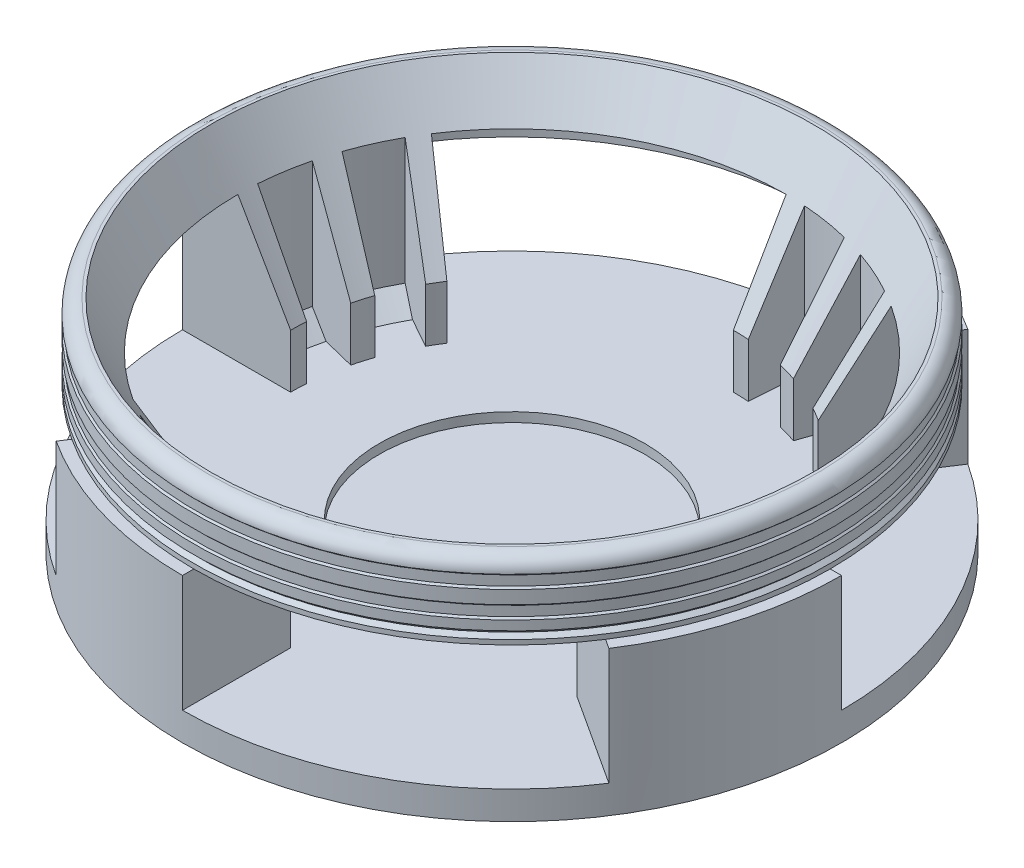
SolidWorks part; units mm, degrees
ref_plane "前视基准面" through (0, 0, 0) normal (0, 0, 1) x (1, 0, 0)
ref_plane "上视基准面" through (0, 0, 0) normal (0, 1, 0) x (1, 0, 0)
ref_plane "右视基准面" through (0, 0, 0) normal (1, 0, 0) x (0, 0, -1)
sketch "草图1" plane through (0, 0, 0) normal (0, 1, 0) x (1, 0, 0)
  circle A0 centre (0, 0) radius 35
  dimension "D1" = 70
extrude "凸台-拉伸1" add sketch "草图1" along normal blind 3
sketch "草图2" plane through (0, 3, 0) normal (0, 1, 0) x (1, 0, 0)
  line L0 (0, 32) -> (0, 35)
  line L1 (17.4284, 26.8375) -> (19.0624, 29.3535)
  line L2 (32, 0) -> (35, 0)
  line L3 (26.8375, -17.4284) -> (29.3535, -19.0624)
  line L4 (0, -32) -> (0, -35)
  line L5 (-17.4284, -26.8375) -> (-19.0624, -29.3535)
  line L6 (-32, 0) -> (-35, 0)
  line L7 (-26.8375, 17.4284) -> (-29.3535, 19.0624)
  circle A0 centre (0, 0) radius 35
  circle A1 centre (0, 0) radius 32
  circle A2 centre (0, 0) radius 35 construction
  point P21 (0, 0)
  point P25 (0, 0)
  dimension "D1" = 3
  dimension "D3" = 33
  dimension "D2" = 33
  dimension "D4" = 33
  dimension "D5" = 33
extrude "凸台-拉伸2" add sketch "草图2" along normal blind 20.4
sketch "草图3" plane through (0, 3, 0) normal (0, 1, 0) x (1, 0, 0)
  circle A0 centre (0, 0) radius 14.1
  dimension "D1" = 28.2
extrude "切除-拉伸1" cut sketch "草图3" against normal blind 1
sketch "草图4" plane through (0, 23.4, 0) normal (0, 1, 0) x (1, 0, 0)
  circle A0 centre (0, 0) radius 35
  circle A1 centre (0, 0) radius 33.8
  arc A3 (29.3535, -19.0624) -> (35, 0) centre (0, 0) ccw construction
  dimension "D1" = 1.2
extrude "切除-拉伸2" cut sketch "草图4" against normal blind 8
fillet "圆角1" radius 1.5 4 edges at (-32.4081, 23.4, -9.5997) (9.5997, 23.4, -32.4081) (32.4081, 23.4, 9.5997) (-9.5997, 23.4, 32.4081)
chamfer "倒角1" distance 20.4 angle 30 4 edges at (9.0885, 3, -30.6822) (-9.0885, 3, 30.6822) (30.6822, 3, 9.0885) (-30.6822, 3, -9.0885) first distance on face at (8.9014, 13.2, -30.0505) first distance on face at (-8.9014, 13.2, 30.0505) first distance on face at (30.0505, 13.2, 8.9014) first distance on face at (-30.0505, 13.2, -8.9014)
sketch "草图10" plane through (0, 0, 0) normal (0.8387, 0, 0.5446) x (0.5446, 0, -0.8387)
  line L0 (32, 23.4) -> (29.1132, 18.4)
  line L1 (33.8, 21.9) -> (33.8, 15.4)
  line L2 (32, 23.4) -> (32.3, 23.4)
  line L3 (29.1132, 18.4) -> (30.2679, 18.4)
  line L4 (30.2679, 18.4) -> (31.3732, 20.3144)
  line L5 (33.8, 15.4) -> (32.3, 15.4)
  line L6 (32.3, 15.4) -> (32.3, 20.0661)
  line L7 (33.8, 21.9) -> (33.8, 15.4) construction
  line L8 (32, 23.4) -> (26.8375, 23.4) construction
  line L9 (32, 23.4) -> (20.2221, 3) construction
  line L10 (33.8, 15.4) -> (35, 15.4) construction
  line L12 (0, 0) -> (0, 39.3433) construction
  arc A0 (32.3, 20.0661) -> (31.3732, 20.3144) centre (31.8033, 20.0661) ccw
  arc A1 (33.8, 21.9) -> (32.3, 23.4) centre (32.3, 21.9) ccw
  arc A2 (33.8, 21.9) -> (32.3, 23.4) centre (32.3, 21.9) ccw construction
  dimension "D1" = 5
  dimension "D2" = 1
  dimension "D3" = 1.9
revolve "旋转2" add sketch "草图10" angle 360 about L12
sketch "草图6" plane through (0, 23.4, 0) normal (0, 1, 0) x (1, 0, 0)
  line L0 (0, 20.2221) -> (0, 29.1132)
  line L1 (1.4106, 20.1728) -> (2.0308, 29.0423)
  line L2 (9.8038, 17.6866) -> (14.1144, 25.463)
  line L3 (11.0137, 16.9596) -> (15.8562, 24.4164)
  line L4 (7.0431, 28.2485) -> (4.8922, 19.6214)
  line L5 (6.5837, 19.1203) -> (9.4783, 27.5271)
  line L6 (16.9596, -11.0137) -> (24.4164, -15.8562)
  line L7 (17.6866, -9.8038) -> (25.463, -14.1144)
  line L8 (19.1203, -6.5837) -> (27.5271, -9.4783)
  line L9 (28.2485, -7.0431) -> (19.6214, -4.8922)
  line L10 (20.1728, -1.4106) -> (29.0423, -2.0308)
  line L11 (20.2221, 0) -> (29.1132, 0)
  line L12 (-11.0137, -16.9596) -> (-15.8562, -24.4164)
  line L13 (-9.8038, -17.6866) -> (-14.1144, -25.463)
  line L14 (-6.5837, -19.1203) -> (-9.4783, -27.5271)
  line L15 (-7.0431, -28.2485) -> (-4.8922, -19.6214)
  line L16 (-21.6701, -19.4419) -> (-21.6916, -19.4749)
  line L17 (-1.4106, -20.1728) -> (-2.0308, -29.0423)
  line L18 (0, -20.2221) -> (0, -29.1132)
  line L19 (-16.9596, 11.0137) -> (-24.4164, 15.8562)
  line L20 (-17.6866, 9.8038) -> (-25.463, 14.1144)
  line L21 (-19.1203, 6.5837) -> (-27.5271, 9.4783)
  line L22 (-28.2485, 7.0431) -> (-19.6214, 4.8922)
  line L23 (-20.1728, 1.4106) -> (-29.0423, 2.0308)
  line L24 (-20.2221, 0) -> (-29.1132, 0)
  circle A0 centre (0, 0) radius 29.1132
  circle A1 centre (0, 0) radius 20.2221
  arc A2 (29.1132, 0) -> (15.8562, 24.4164) centre (0, 0) ccw construction
  arc A5 (11.0137, 16.9596) -> (0, 20.2221) centre (0, 0) ccw construction
  point P60 (0, 0)
  point P61 (0, 0)
  point P65 (0, 0)
  point P74 (-3.092, 2.2023)
  point P123 (0, 0)
  dimension "D1" = 4
  dimension "D2" = 4
  dimension "D3" = 10
  dimension "D4" = 10
  dimension "D5" = 4
extrude "切除-拉伸3" cut sketch "草图6" against normal up to surface (20.4 mm away) contours A1 L22 A0 L23 | A1 L20 A0 L21 | A1 L13 A0 L14 | A1 L15 A0 L17 | A1 L7 A0 L8 | A1 L9 A0 L10 | A1 L2 A0 L5 | A1 L4 A0 L1 up to face at (0, 3, 14.1)
sketch "草图7" plane through (0, 23.4, 0) normal (0, 1, 0) x (1, 0, 0)
  circle A3 centre (0, 0) radius 23.5132
  arc A4 (29.1132, 0) -> (15.8562, 24.4164) centre (0, 0) ccw construction
  dimension "D1" = 5.6
extrude "切除-拉伸4" cut sketch "草图7" against normal up to surface (20.4 mm away) up to face at (0, 3, 14.1)
chamfer "倒角2" distance 2 angle 45 8 edges at (26.5963, 3, 11.8414) (-4.5543, 3, 28.7548) (-11.8414, 3, 26.5963) (-26.5963, 3, -11.8414) (4.5543, 3, -28.7548) (11.8414, 3, -26.5963) (28.7548, 3, 4.5543) (-28.7548, 3, -4.5543)
sketch "草图11" plane through (0, 0, 0) normal (0.5446, 0, -0.8387) x (-0.8387, 0, -0.5446)
  line L0 (33.8, 21.9) -> (33.62, 21.72)
  line L1 (33.8, 15.4) -> (33.8, 21.9) construction
  line L2 (33.62, 21.72) -> (33.62, 20.68)
  line L3 (33.62, 20.68) -> (33.8, 20.5)
  line L4 (33.8, 20.5) -> (33.8, 21.9)
  line L5 (33.8, 19.1) -> (33.62, 18.92)
  line L6 (33.62, 18.92) -> (33.62, 17.88)
  line L7 (33.62, 17.88) -> (33.8, 17.7)
  line L8 (33.8, 17.7) -> (33.8, 19.1)
  line L9 (33.8, 16.7) -> (33.4, 16.3)
  line L10 (33.4, 16.3) -> (33.8, 15.9)
  line L11 (33.8, 15.9) -> (33.8, 16.7)
  line L12 (33.8, 15.4) -> (35, 15.4) construction
  line L13 (0, 0) -> (0, 39.9244) construction
  line L14 (33.8, 21.9) -> (33.8, 15.4) construction
  point P14 (33.8, 21.9)
  dimension "D1" = 1.4
  dimension "D2" = 1.4
  dimension "D3" = 1.4
  dimension "D4" = 0.18
  dimension "D5" = 45
  dimension "D6" = 0.18
  dimension "D7" = 0.8
  dimension "D8" = 0.5
revolve "切除-旋转1" cut sketch "草图11" angle 360 about L13
